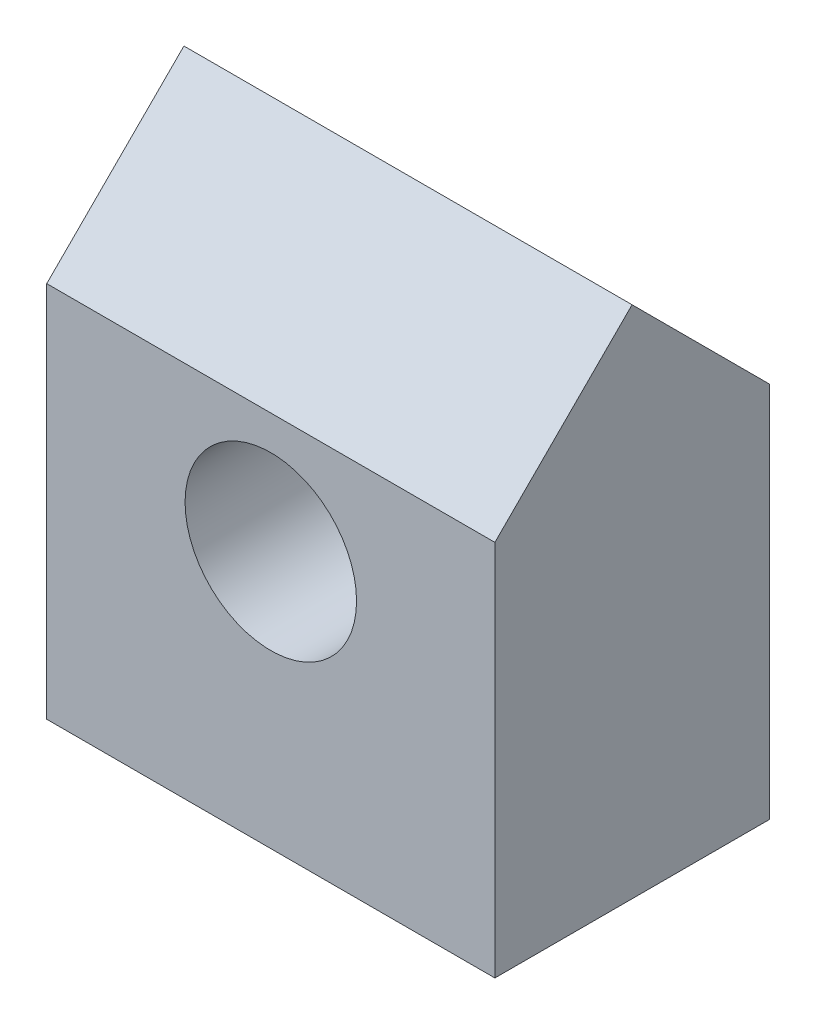
SolidWorks part; units mm, degrees
ref_plane "前视基准面" through (0, 0, 0) normal (0, 0, 1) x (1, 0, 0)
ref_plane "上视基准面" through (0, 0, 0) normal (0, 1, 0) x (1, 0, 0)
ref_plane "右视基准面" through (0, 0, 0) normal (1, 0, 0) x (0, 0, -1)
other "Configuration Table"
sketch "草图1" plane through (0, 0, 0) normal (0, 1, 0) x (1, 0, 0)
  line L1 (0, 0) -> (3.92, 0)
  line L2 (0, 0) -> (0, -2.4)
  line L3 (0, -2.4) -> (3.92, -2.4)
  line L4 (3.92, 0) -> (3.92, -2.4)
  dimension "D1" = 3.92
  dimension "D2" = 2.4
extrude "凸台-拉伸1" add sketch "草图1" along normal blind 4.5
sketch "草图2" plane through (0, 0, 2.4) normal (0, 0, 1) x (1, 0, 0)
  line L0 (0, 4.5) -> (0, 0) construction
  line L1 (0, 0) -> (3.92, 0) construction
  circle A0 centre (1.96, 2.25) radius 0.75
  dimension "D3" = 1.5
  dimension "D1" = 1.96
  dimension "D2" = 2.25
extrude "切除-拉伸1" cut sketch "草图2" against normal blind 4.5
chamfer "倒角1" distance 1.2 angle 45 2 edges at (1.96, 4.5, 0) (1.96, 4.5, 2.4)
